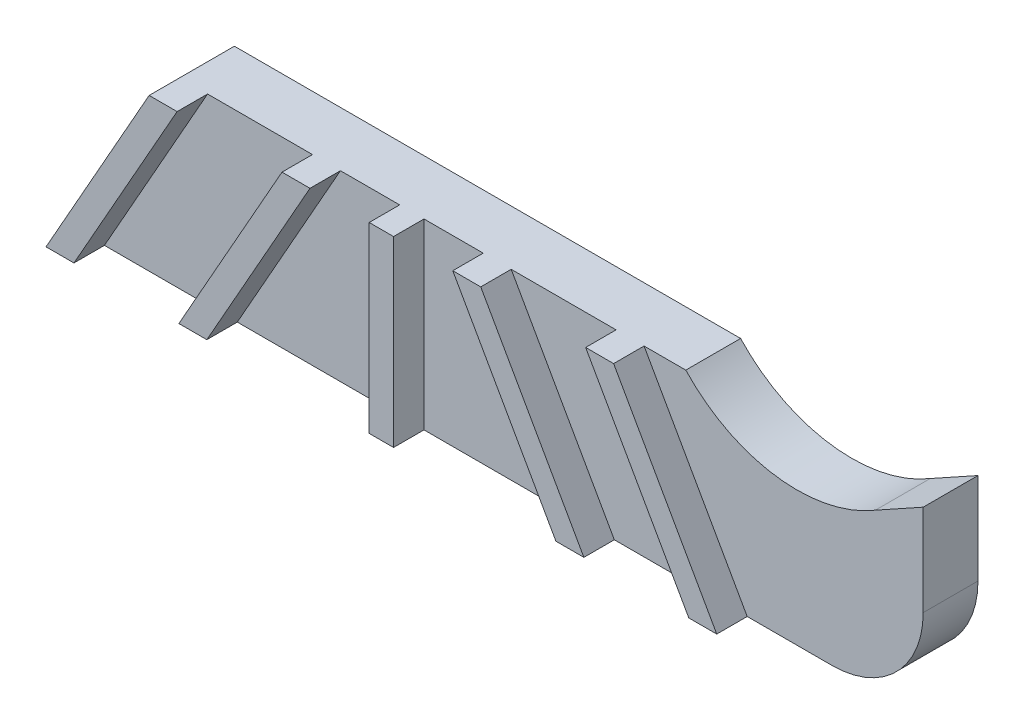
SolidWorks part; units mm, degrees
ref_plane "Front Plane" through (0, 0, 0) normal (1, 0, 0) x (0, 1, 0)
ref_plane "Top Plane" through (0, 0, 0) normal (0, 0, 1) x (0, 1, 0)
ref_plane "Right Plane" through (0, 0, 0) normal (0, 1, 0) x (-1, 0, 0)
sketch "Sketch1" plane through (0, 0, 0) normal (0, 0, 1) x (0, 1, 0)
  line L0 (-2.1229, 14.2549) -> (-2.1229, -10.5533)
  line L1 (0.8771, -13.5533) -> (3.8771, -13.5533)
  line L2 (3.8771, -13.5533) -> (3.0064, -11.9839)
  line L3 (3.8771, -5.7568) -> (3.8771, 10.8675)
  line L4 (3.8771, 10.8675) -> (-2.1229, 14.2549)
  arc A0 (-2.1229, -10.5533) -> (0.8771, -13.5533) centre (0.8771, -10.5533) ccw
  arc A1 (3.8771, -5.7568) -> (3.0064, -11.9839) centre (7.2923, -9.4087) ccw
  dimension "D1" = 6
extrude "Boss-Extrude1" add sketch "Sketch1" along normal blind 2.8
sketch "Sketch2" plane through (0, 0, 2.8) normal (0, 0, 1) x (1, 0, 0)
  line L0 (-9.9488, 3.8771) -> (-13.3362, -2.1229)
  line L1 (5.7568, 3.8771) -> (-10.8675, 3.8771) construction
  line L2 (-14.2549, -2.1229) -> (10.5533, -2.1229) construction
  line L3 (-10.8675, 3.8771) -> (-14.2549, -2.1229) construction
  line L4 (-6.5038, 3.8771) -> (-9.8912, -2.1229)
  line L5 (-8.9725, -2.1229) -> (-5.5851, 3.8771)
  line L6 (-0.8961, 3.8771) -> (-2.8406, 3.8771)
  line L7 (-3.6406, 3.8771) -> (-3.6406, -2.1229)
  line L8 (2.4913, -2.1229) -> (-2.8406, -2.1229)
  line L9 (-3.6406, 3.8771) -> (-2.8406, 3.8771) construction
  line L10 (-3.2406, 3.8771) -> (-3.2406, -2.1229) construction
  line L11 (-9.9488, 3.8771) -> (-6.5038, 3.8771)
  line L12 (-13.3362, -2.1229) -> (-9.8912, -2.1229)
  line L13 (-8.9725, -2.1229) -> (-3.6406, -2.1229)
  line L14 (-5.5851, 3.8771) -> (-3.6406, 3.8771)
  line L15 (6.8551, -2.1229) -> (3.41, -2.1229)
  line L16 (3.4677, 3.8771) -> (0.0226, 3.8771)
  line L17 (-2.8406, 3.8771) -> (-2.8406, -2.1229)
  line L18 (2.4913, -2.1229) -> (-0.8961, 3.8771)
  line L19 (0.0226, 3.8771) -> (3.41, -2.1229)
  line L20 (3.4677, 3.8771) -> (6.8551, -2.1229)
  line L21 (4.3864, 3.8771) -> (7.7738, -2.1229)
  line L22 (4.3864, 3.8771) -> (13.5533, 3.8771)
  line L23 (13.5533, 3.8771) -> (13.5533, -2.1229)
  line L24 (13.5533, -2.1229) -> (7.7738, -2.1229)
  dimension "D1" = 0.8
  dimension "D2" = 3
  dimension "D3" = 0.8
  dimension "D4" = 0.8
  dimension "D5" = 0.4
extrude "Cut-Extrude1" cut sketch "Sketch2" against normal blind 1
